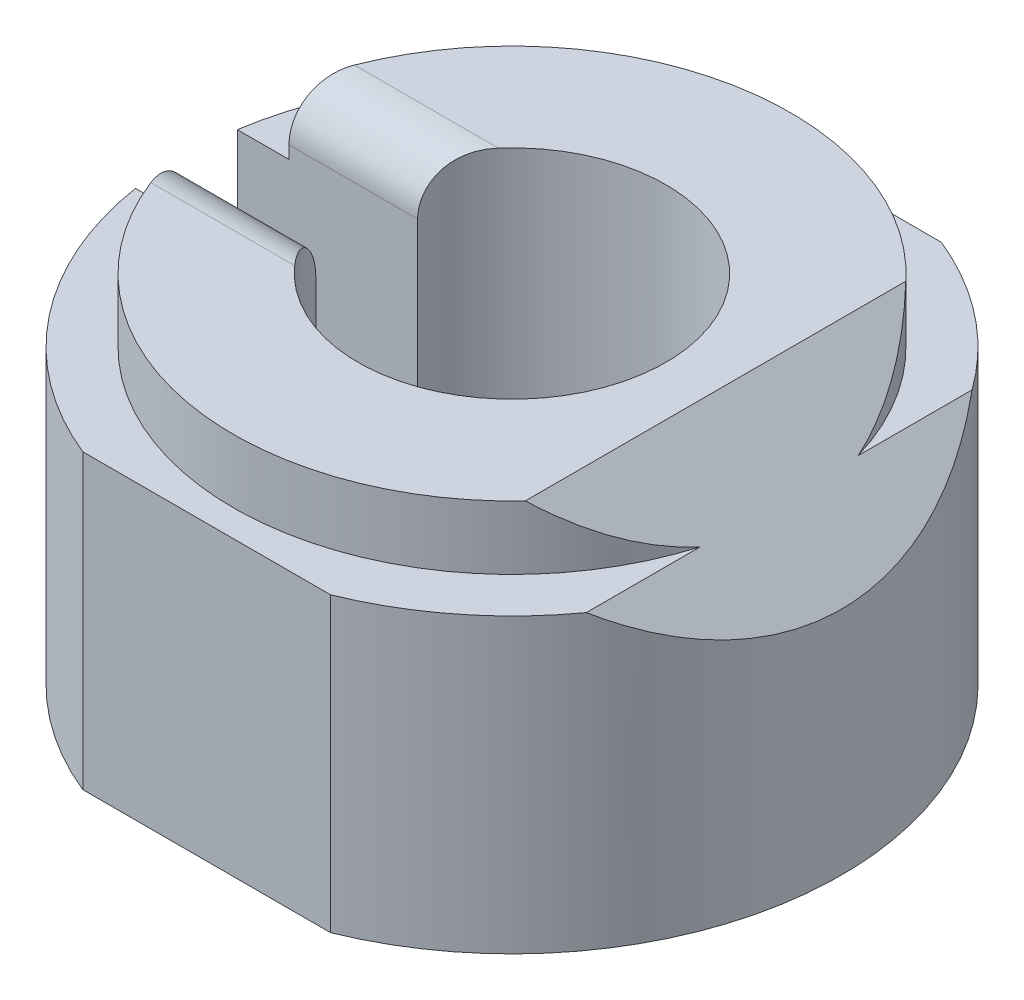
SolidWorks part; units mm, degrees
ref_plane "Front Plane" through (0, 0, 0) normal (0, 0, 1) x (1, 0, 0)
ref_plane "Top Plane" through (0, 0, 0) normal (0, 1, 0) x (1, 0, 0)
ref_plane "Right Plane" through (0, 0, 0) normal (1, 0, 0) x (0, 0, -1)
sketch "Sketch1" plane through (0, 0, 0) normal (0, 1, 0) x (1, 0, 0)
  circle A0 centre (0, 0) radius 6.05
  circle A1 centre (0, 0) radius 10.95
  dimension "D1" = 12.1
  dimension "D2" = 21.9
extrude "Boss-Extrude1" add sketch "Sketch1" against normal blind 2 contours A1 A0 | A0 | A0 | A1 region at (0, 0, 0) region at (-10.6403, 0, 0)
extrude "Boss-Extrude2" add sketch "Sketch1<3>" along normal blind 12
sketch "Sketch1<3>" plane through (0, 0, 0) normal (0, 1, 0) x (1, 0, 0) same geometry as "Sketch1"
sketch "Sketch2" plane through (0, 12, 0) normal (0, 1, 0) x (1, 0, 0)
  circle A0 centre (0, 0) radius 10.95
  circle A1 centre (0, 0) radius 12.95
  circle A2 centre (0, 0) radius 10.95 construction
  dimension "D1" = 2
extrude "Boss-Extrude3" add sketch "Sketch2" against normal up to surface (14 mm away) from offset 2.5 up to face at (0, -2, 10.95) offset against normal yes
sketch "Sketch3" plane through (0, 0, 0) normal (0, 1, 0) x (1, 0, 0)
  line L0 (-50, 12) -> (-50, 36)
  line L1 (-50, -12) -> (50, -12)
  line L2 (-50, -12) -> (-50, 12)
  line L3 (-50, 12) -> (50, 12)
  line L4 (50, -12) -> (50, 12)
  line L5 (-50, -12) -> (50, 12) construction
  line L6 (-50, 12) -> (50, -12) construction
  line L7 (-50, 12) -> (50, 12)
  line L8 (-50, 36) -> (50, 36)
  line L9 (50, 12) -> (50, 36)
  line L10 (50, -12) -> (-50, -12)
  line L11 (50, -12) -> (50, -36)
  line L12 (-50, -12) -> (-50, -36)
  line L13 (50, -36) -> (-50, -36)
  point P0 (0, 0)
  dimension "D1" = 24
  dimension "D2" = 100
extrude "Cut-Extrude1" cut sketch "Sketch3" against normal through all both and the other way through all contours L13 L11 L1 L12 | L3 L9 L8 L0 | L0 L7 L9 L8 region at (0, 0, -24) region at (0, 0, 24)
sketch "Sketch4" plane through (0, 0, 0) normal (0, 0, 1) x (1, 0, 0)
  line L0 (5, 15) -> (13, 7)
  line L1 (0, 0) -> (13, 0)
  line L2 (0, 0) -> (0, 15)
  line L3 (0, 15) -> (13, 15)
  line L4 (13, 0) -> (13, 15)
  line L5 (13, 7) -> (5, 7)
  line L6 (13, 7) -> (13, 15)
  line L7 (13, 15) -> (5, 15)
  line L8 (5, 7) -> (5, 15)
  dimension "D1" = 13
  dimension "D2" = 15
  dimension "D3" = 5
extrude "Cut-Extrude3" cut sketch "Sketch4" against normal through all both and the other way through all contours L0 L4 L3 region at (10.3333, 12.3333, 0)
sketch "Sketch5" plane through (0, 0, 0) normal (0, 1, 0) x (1, 0, 0)
  line L0 (-2, -2) -> (-2, 2)
  line L1 (2, 2) -> (-2, 2)
  line L2 (2, 2) -> (2, -2)
  line L3 (2, -2) -> (-2, -2)
  line L4 (-2, 2) -> (-2, -2)
  line L5 (2, 2) -> (-2, -2) construction
  line L6 (2, -2) -> (-2, 2) construction
  line L7 (-2, -2) -> (-20, -2)
  line L8 (-2, 2) -> (-20, 2)
  line L9 (-20, -2) -> (-20, 2)
  point P0 (0, 0)
  dimension "D1" = 4
  dimension "D2" = 20
extrude "Cut-Extrude4" cut sketch "Sketch5" along normal through all contours L9 L7 L0 L8 region at (-11, 0, 0)
fillet "Fillet1" radius 2 4 edges at (-8.2378, 12, 2) (-8.2378, 12, -2) (-9.2522, 0, -2) (-9.2522, 0, 2)
sketch "Sketch6" plane through (0, 0, 0) normal (0, 1, 0) x (1, 0, 0)
  circle A0 centre (0, 0) radius 1.6
  dimension "D1" = 3.2
extrude "Cut-Extrude5" cut sketch "Sketch6" against normal through all both and the other way through all
